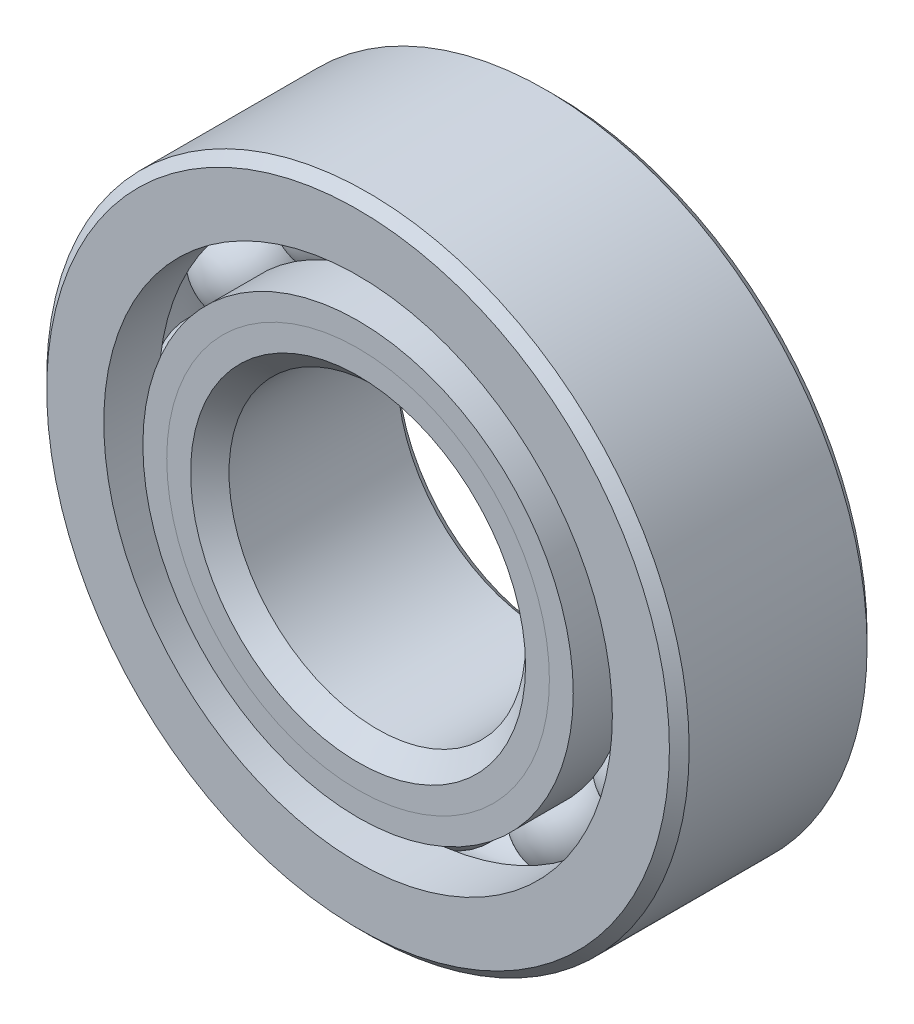
SolidWorks part; units mm, degrees
material "Alloy Steel"
ref_plane "Front Plane" through (0, 0, 0) normal (0, 0, 1) x (1, 0, 0)
ref_plane "Top Plane" through (0, 0, 0) normal (0, 1, 0) x (1, 0, 0)
ref_plane "Right Plane" through (0, 0, 0) normal (1, 0, 0) x (0, 0, -1)
sketch "Sketch1" plane through (0, 0, 0) normal (1, 0, 0) x (0, 0, -1)
  line L0 (-6.35, 0) -> (6.35, 0) construction
  line L1 (0, 20.6375) -> (0, -20.6375) construction
  line L2 (5.715, 20.6375) -> (-5.715, 20.6375)
  line L3 (-5.715, 20.6375) -> (-6.35, 20.0025)
  line L4 (-6.35, 20.0025) -> (-6.35, 16.3373)
  line L5 (-6.35, 16.3373) -> (-2.8222, 16.3373)
  line L6 (6.35, 16.3373) -> (2.8222, 16.3373)
  line L7 (6.35, 20.0025) -> (6.35, 16.3373)
  line L8 (5.715, 20.6375) -> (6.35, 20.0025)
  line L9 (0, 20.6375) -> (0, 15.0812) construction
  line L10 (0, 15.0812) -> (0, 9.525) construction
  arc A0 (-2.8222, 16.3373) -> (2.8222, 16.3373) centre (0, 15.0812) cw
  point P14 (0, 9.525)
  dimension "Width" = 12.7
  dimension "OD" = 41.275
  dimension "D1" = 45
  dimension "D2" = 0.635
  dimension "D3" = 5.6444
  dimension "D4" = 1.256
revolve "Revolve1" add sketch "Sketch1" angle 360 about L0
sketch "Sketch2" plane through (0, 0, 0) normal (1, 0, 0) x (0, 0, -1)
  line L0 (-6.35, 13.8252) -> (-2.8222, 13.8252)
  line L1 (-6.35, 20.0025) -> (-6.35, -20.0025) construction
  line L2 (-6.35, 13.8252) -> (-6.35, 12.2919)
  line L3 (-6.35, 12.2919) -> (-4.8167, 10.7586)
  line L4 (-4.8167, 10.7586) -> (0, 10.7586)
  line L5 (0, 20.6375) -> (0, -20.6375) construction
  line L6 (0, 10.7586) -> (0, 11.9921)
  line L7 (0, 11.9921) -> (0, 9.525) construction
  line L8 (-6.35, 13.8252) -> (-6.35, 10.7586) construction
  line L9 (-6.35, 10.7586) -> (-4.8167, 10.7586) construction
  arc A0 (-2.8222, 13.8252) -> (0, 11.9921) centre (0, 15.0812) ccw
  arc A1 (2.8222, 16.3373) -> (-2.8222, 16.3373) centre (0, 15.0812) ccw construction
  circle A2 centre (0, 15.0812) radius 3.0891 construction
  dimension "D1" = 45
revolve "Revolve2" add sketch "Sketch2" angle 360 about L0
sketch "Sketch3" plane through (0, 0, 0) normal (1, 0, 0) x (0, 0, -1)
  line L0 (-6.35, 12.2919) -> (-4.8167, 10.7586)
  line L1 (-4.8167, 10.7586) -> (0, 10.7586)
  line L2 (0, 10.7586) -> (0, 11.9921)
  line L3 (-6.35, 12.2919) -> (-6.35, 10.7586)
  line L4 (-6.35, 13.8252) -> (-6.35, 10.7586) construction
  line L5 (-6.35, 10.7586) -> (-5.1164, 9.525)
  line L6 (-5.1164, 9.525) -> (5.715, 9.525)
  line L7 (5.715, 20.6375) -> (5.715, -20.6375) construction
  line L8 (5.715, 9.525) -> (6.35, 10.16)
  line L9 (6.35, -20.0025) -> (6.35, 20.0025) construction
  line L10 (6.35, 10.16) -> (6.35, 13.8252)
  line L11 (6.35, 13.8252) -> (2.8222, 13.8252)
  line L13 (5.715, 20.6375) -> (6.35, 20.0025) construction
  circle A0 centre (0, 15.0812) radius 3.0891 construction
  arc A1 (2.8222, 13.8252) -> (0, 11.9921) centre (0, 15.0812) cw
revolve "Revolve3" add sketch "Sketch3" angle 360 about L0
sketch "Sketch4" plane through (0, 0, 0) normal (1, 0, 0) x (0, 0, -1)
  line L0 (-3.0891, 15.0812) -> (3.0891, 15.0812)
  circle A1 centre (0, 15.0812) radius 3.0891 construction
  arc A2 (-3.0891, 15.0812) -> (3.0891, 15.0812) centre (0, 15.0812) cw
  arc A3 (2.8222, 16.3373) -> (-2.8222, 16.3373) centre (0, 15.0812) ccw construction
revolve "Revolve4" add sketch "Sketch4" angle 360 about L0
ref_axis "Axis1" through (0, 0, -6.35) along (0, 0, 1)
pattern_circular "CirPattern1" count 12 every 30 about axis through (0, 0, -6.35) along (0, 0, 1) of bodies 104
equation "\"D2@Sketch1\" = \"Width@Sketch1\"*.05"
equation "\"D3@Sketch1\" = \"Width@Sketch1\"/2.25"
equation "\"D4@Sketch1\" = (((\"OD@Sketch1\"-\"Width@Sketch1\")/2)/3.25)/3.5"
equation "\"D2@CirPattern1\" = 360/\"Balls@CirPattern1\""
